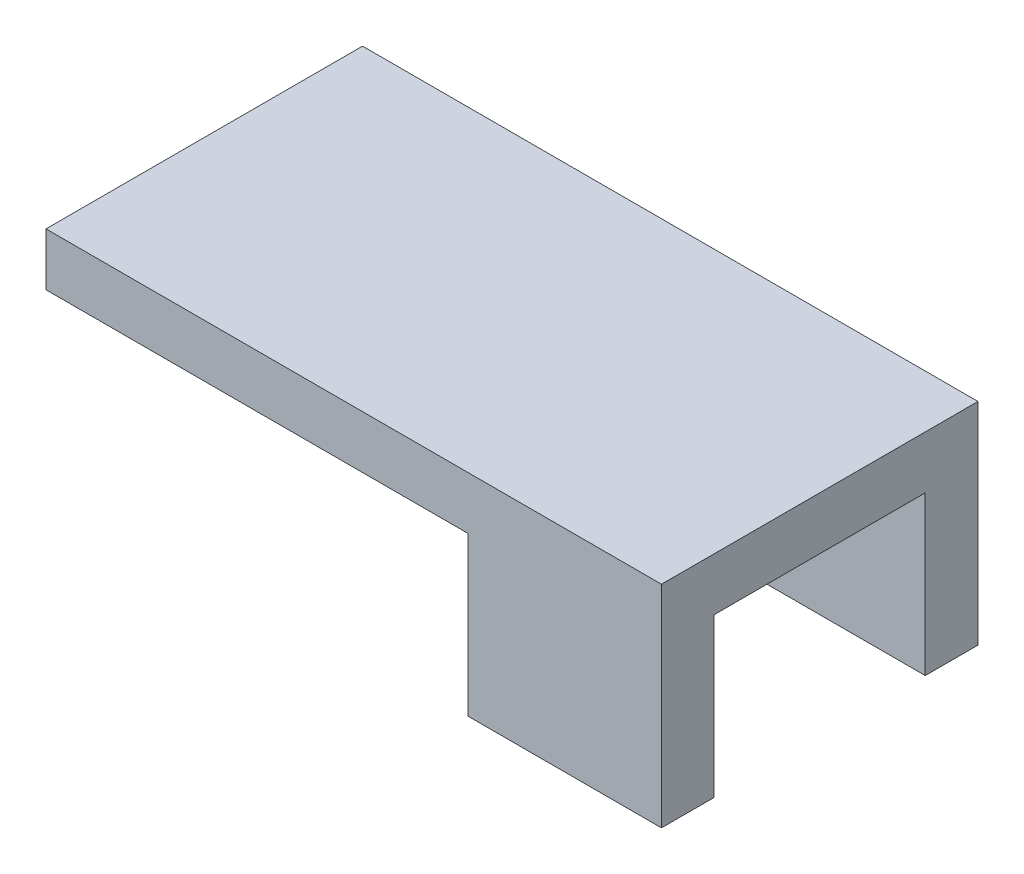
SolidWorks part; units mm, degrees
ref_plane "Front Plane" through (0, 0, 0) normal (0, 0, 1) x (1, 0, 0)
ref_plane "Top Plane" through (0, 0, 0) normal (0, 1, 0) x (1, 0, 0)
ref_plane "Right Plane" through (0, 0, 0) normal (1, 0, 0) x (0, 0, -1)
sketch "Sketch1" plane through (0, 0, 0) normal (0, 1, 0) x (1, 0, 0)
  line L1 (0, 0) -> (35, 0)
  line L2 (0, 0) -> (0, 18)
  line L3 (0, 18) -> (35, 18)
  line L4 (35, 0) -> (35, 18)
  dimension "D1" = 18
  dimension "D2" = 35
extrude "Boss-Extrude1" add sketch "Sketch1" along normal blind 3
sketch "Sketch2" plane through (0, 0, 0) normal (0, -1, 0) x (1, 0, 0)
  line L1 (35, 0) -> (24, 0)
  line L2 (35, 0) -> (35, -3)
  line L3 (35, -3) -> (24, -3)
  line L4 (24, 0) -> (24, -3)
  line L5 (35, -18) -> (24, -18)
  line L6 (35, -18) -> (35, -15)
  line L7 (35, -15) -> (24, -15)
  line L8 (24, -18) -> (24, -15)
  dimension "D1" = 3
  dimension "D2" = 3
  dimension "D3" = 11
  dimension "D4" = 11
extrude "Boss-Extrude2" add sketch "Sketch2" along normal blind 9
